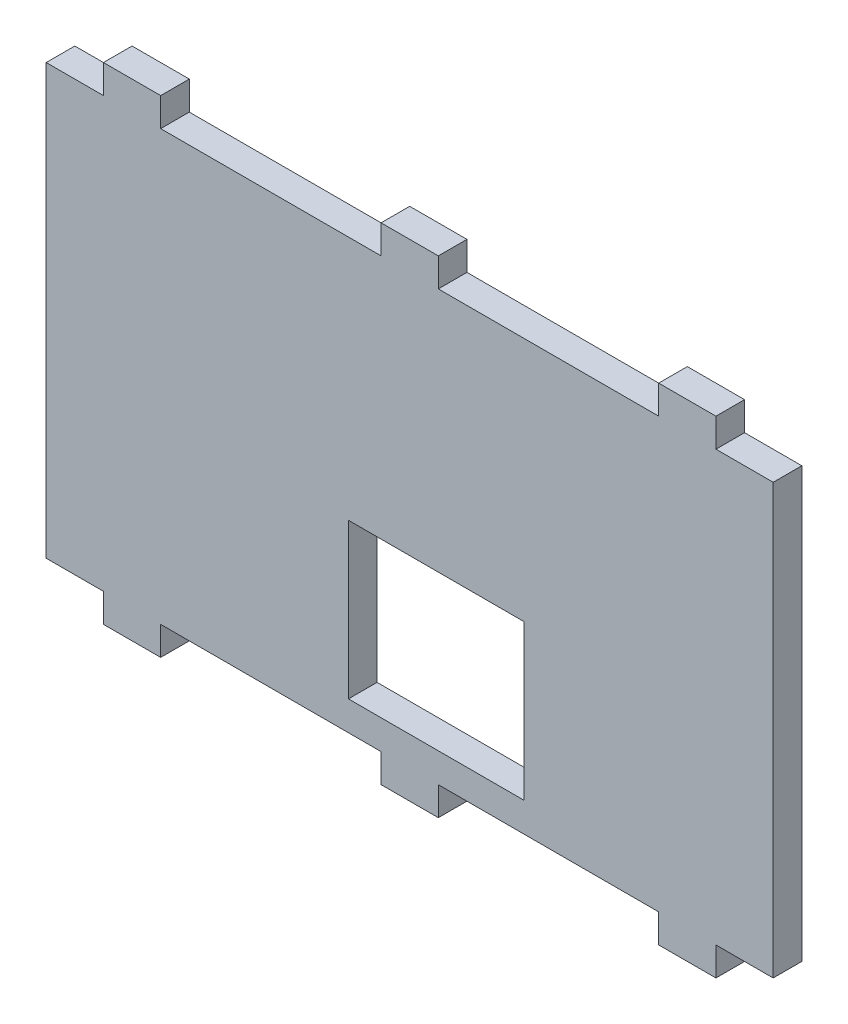
SolidWorks part; units mm, degrees
ref_plane "Plan de face" through (0, 0, 0) normal (0, 0, 1) x (1, 0, 0)
ref_plane "Plan de dessus" through (0, 0, 0) normal (0, 1, 0) x (1, 0, 0)
ref_plane "Plan de droite" through (0, 0, 0) normal (1, 0, 0) x (0, 0, -1)
sketch "Esquisse1" plane through (0, 0, 0) normal (0, 0, 1) x (1, 0, 0)
  line L1 (0, 0) -> (127, 0)
  line L2 (0, 0) -> (0, 75)
  line L3 (0, 75) -> (127, 75)
  line L4 (127, 0) -> (127, 75)
  dimension "D1" = 75
  dimension "D2" = 127
extrude "Boss.-Extru.1" add sketch "Esquisse1" along normal blind 5
sketch "Esquisse2" plane through (0, 0, 5) normal (0, 0, 1) x (1, 0, 0)
  line L0 (127, 75) -> (0, 75) construction
  line L1 (10, 75) -> (20, 75)
  line L2 (10, 75) -> (10, 80)
  line L3 (10, 80) -> (20, 80)
  line L4 (20, 75) -> (20, 80)
  line L5 (0, 0) -> (127, 0) construction
  line L6 (117, 75) -> (107, 75)
  line L7 (117, 75) -> (117, 80)
  line L8 (117, 80) -> (107, 80)
  line L9 (107, 75) -> (107, 80)
  line L10 (58.5, 75) -> (68.5, 75)
  line L11 (58.5, 75) -> (58.5, 80)
  line L12 (58.5, 80) -> (68.5, 80)
  line L13 (68.5, 75) -> (68.5, 80)
  line L14 (63.5, 75) -> (63.5, 0) construction
  line L18 (10, 0) -> (20, 0)
  line L19 (10, 0) -> (10, -5)
  line L20 (10, -5) -> (20, -5)
  line L21 (20, 0) -> (20, -5)
  line L22 (0, 75) -> (0, 0) construction
  line L23 (58.5, 0) -> (68.5, 0)
  line L24 (58.5, 0) -> (58.5, -5)
  line L25 (58.5, -5) -> (68.5, -5)
  line L26 (68.5, 0) -> (68.5, -5)
  line L31 (107, 0) -> (117, 0)
  line L32 (107, 0) -> (107, -5)
  line L33 (107, -5) -> (117, -5)
  line L34 (117, 0) -> (117, -5)
  line L35 (127, 0) -> (127, 75) construction
  dimension "D1" = 10
  dimension "D2" = 5
  dimension "D3" = 10
  dimension "D4" = 10
  dimension "D7" = 10
  dimension "D10" = 10
extrude "Boss.-Extru.2" add sketch "Esquisse2" against normal blind 5
sketch "Esquisse3" plane through (0, 0, 0) normal (0, 0, -1) x (-1, 0, 0)
  line L1 (-83.4871, 32.1492) -> (-52.7971, 32.1492)
  line L2 (-83.4871, 32.1492) -> (-83.4871, 5.1244)
  line L3 (-83.4871, 5.1244) -> (-52.7971, 5.1244)
  line L4 (-52.7971, 32.1492) -> (-52.7971, 5.1244)
extrude "Enlèv. mat.-Extru.1" cut sketch "Esquisse3" against normal blind 5
